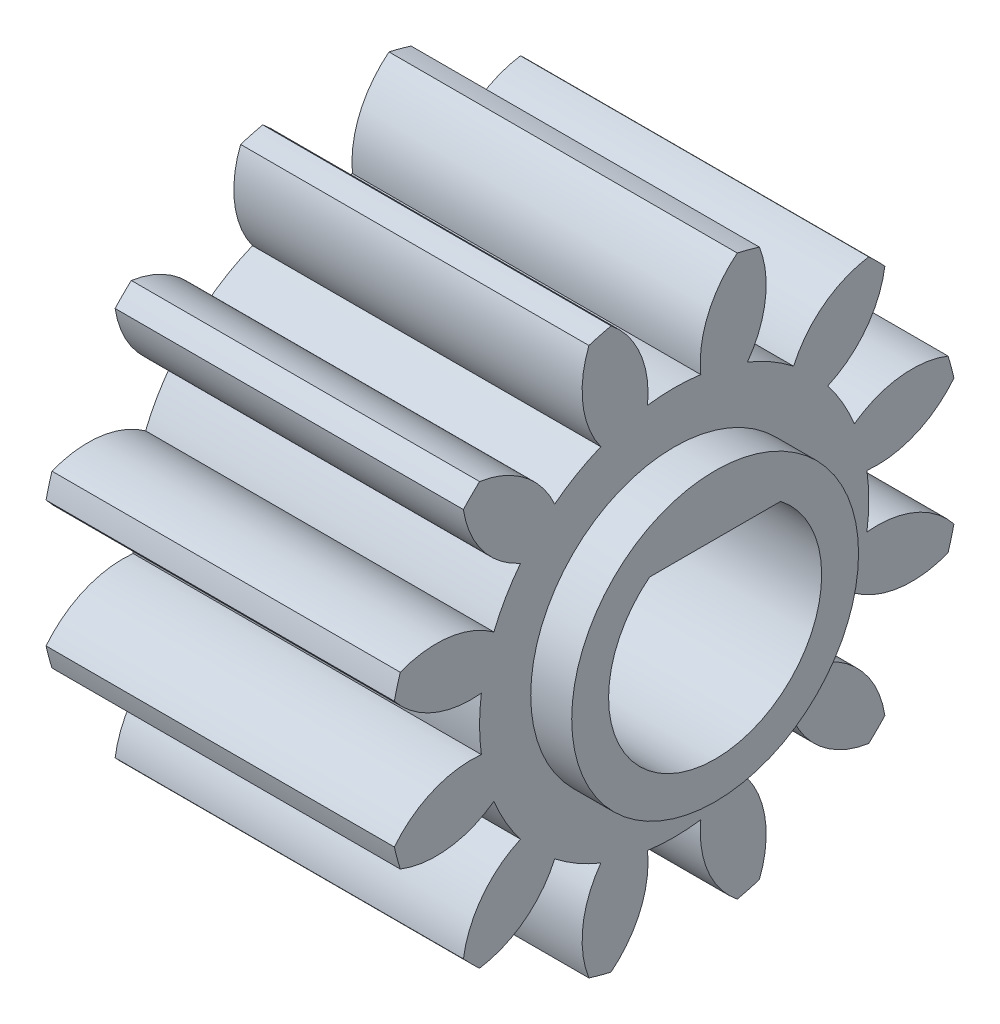
SolidWorks part; units mm, degrees
ref_plane "Plane1" through (0, 0, 0) normal (0, 0, 1) x (1, 0, 0)
ref_plane "Plane2" through (0, 0, 0) normal (0, 1, 0) x (1, 0, 0)
ref_plane "Plane3" through (0, 0, 0) normal (1, 0, 0) x (0, 0, -1)
sketch "HoldingSke" plane through (0, 0, 0) normal (0, 1, 0) x (1, 0, 0)
  line L0 (0, 0) -> (0.9781, -0.2079)
  line L1 (-15, 0) -> (100, 0) construction
  line L2 (0, 0) -> (-2.1039, 2.3779)
  line L3 (0, 0) -> (-11.863, 4.5341)
  line L4 (0, 0) -> (8.4473, 1.7955)
  line L5 (0, 0) -> (-46.8476, -17.4728)
  line L6 (0, 0) -> (-8.2896, -5.593)
  line L7 (-2.1039, 2.3779) -> (8.6586, 51.2059)
  line L8 (-76.2, 54.61) -> (-75.3, 54.61)
  line L9 (-67.7845, 28.3722) -> (-49.3413, 33.142)
  line L10 (-76.2, 71.12) -> (104.1128, 71.12)
  line L11 (0, 0) -> (-10, 0)
  line L12 (-76.2, 101.6) -> (-76.162, 101.6)
  line L13 (24.9733, 27.94) -> (52.9518, 28.4284)
  line L14 (24.9733, 27.94) -> (24.9743, 27.94)
  line L15 (24.9733, 27.94) -> (100.4006, 29.5858)
  line L16 (-63.627, -1) -> (-12.827, -1)
  circle A0 centre (0, 0) radius 2.5
  circle A1 centre (0, 0) radius 4.749
  circle A2 centre (0, 0) radius 37.5
  circle A3 centre (0, 0) radius 2.5
  dimension "Num_teeth" = 12
  dimension "Pitch_radius" = 180.3128
  dimension "Width" = 10
sketch "BasProSke" plane through (0, 0, 0) normal (0, 1, 0) x (1, 0, 0)
  line L0 (-10, 0) -> (60, 0) construction
  line L1 (0, 0) -> (0, 7)
  line L2 (0, 0) -> (8.5, 0)
  line L3 (8.5, 0) -> (8.5, 7)
  line L4 (8.5, 7) -> (0, 7)
  dimension "Thickness" = 8.5
  dimension "Diameter" = 14
revolve "Base-Revolve" add sketch "BasProSke" angle 360 about L0
sketch "TooCutSke" plane through (0, 0, 0) normal (1, 0, 0) x (0, 0, -1)
  line L1 (0, 0) -> (0, 107) construction
  line L2 (0, 0) -> (-0.8496, 5.9395) construction
  line L3 (0, 0) -> (-3.0836, 11.5081) construction
  line L4 (-0.8496, 5.9395) -> (-1.5418, 5.7541) construction
  arc A0 (0.6497, 4.7044) -> (-0.6497, 4.7044) centre (0, 0) ccw
  arc A1 (1.5664, 6.8486) -> (-1.5664, 6.8486) centre (0, 0) ccw
  circle A2 centre (0, 0) radius 6 construction
  circle A3 centre (0, 0) radius 5.8089 construction
  arc A4 (-0.6497, 4.7044) -> (-1.5664, 6.8486) centre (-3.0369, 4.9518) ccw
  arc A5 (1.5664, 6.8486) -> (0.6497, 4.7044) centre (3.0369, 4.9518) ccw
extrude "ToothCut" cut sketch "TooCutSke" along normal through all
fillet "Breaks" [suppressed] radius 0.02 tangent propagation no
fillet "RootFillets" [suppressed] radius 0.251
pattern_circular "TeethCuts" count 12 every 30 about axis through (-10, 0, 0) along (1, 0, 0) of "ToothCut", "RootFillets", "Breaks"
sketch "HubNeaOneSke" plane through (0, 0, 0) normal (-1, 0, 0) x (0, 0, 1)
  circle A0 centre (0, 0) radius 4.749
  dimension "Diameter" = 9.498
extrude "HubNearOne" [suppressed] add sketch "HubNeaOneSke" along normal blind 41.5001
sketch "HubNeaBotSke" plane through (0, 0, 0) normal (-1, 0, 0) x (0, 0, 1)
  circle A0 centre (0, 0) radius 4.749
  dimension "Diameter" = 9.498
extrude "HubNearBoth" [suppressed] add sketch "HubNeaBotSke" along normal blind 20.75
ref_plane "FarPln" through (8.5, 0, 0) normal (1, 0, 0) x (0, 0, -1)
sketch "HubFarSke" plane through (8.5, 0, 0) normal (1, 0, 0) x (0, 0, -1)
  circle A0 centre (0, 0) radius 4.749
  dimension "Diameter" = 9.498
extrude "HubFar" [suppressed] add sketch "HubFarSke" along normal blind 20.75
sketch "BorSke" plane through (0, 0, 0) normal (1, 0, 0) x (0, 0, -1)
  circle A0 centre (0, 0) radius 2.6
  dimension "Diameter" = 5.2
extrude "Bore" cut sketch "BorSke" along normal mid plane 100.0001
sketch "KeySke" plane through (0, 0, 0) normal (1, 0, 0) x (0, 0, -1)
  line L0 (-1, 0) -> (-1, 3.4)
  line L1 (-1, 3.4) -> (1, 3.4)
  line L2 (1, 3.4) -> (1, 0)
  line L3 (0, 0) -> (0, 34) construction
  line L4 (-1, 0) -> (1, 0)
  dimension "Width" = 2
extrude "Keyway" [suppressed] cut sketch "KeySke" along normal mid plane 100.0001
pattern_circular "Keyway2" [suppressed] count 2 every 90 about axis through (-10, 0, 0) along (1, 0, 0) reverse direction yes
sketch "Sketch1" plane through (8.5, 0, 0) normal (1, 0, 0) x (0, 0, -1)
  line L0 (-1.5992, 2.05) -> (1.5992, 2.05)
  circle A0 centre (0, 0) radius 2.6 construction
  arc A1 (1.5992, 2.05) -> (-1.5992, 2.05) centre (0, 0) ccw
  dimension "D1" = 2.05
extrude "Boss-Extrude1" add sketch "Sketch1" against normal up to surface (8.5 mm away) up to face at (0, 0, -2.6)
sketch "Sketch2" plane through (8.5, 0, 0) normal (1, 0, 0) x (0, 0, -1)
  line L0 (-1.5992, 2.05) -> (1.5992, 2.05) construction
  line L1 (-1.5992, 2.05) -> (1.5992, 2.05)
  circle A0 centre (0, 0) radius 3.5
  arc A1 (-1.5992, 2.05) -> (1.5992, 2.05) centre (0, 0) ccw construction
  arc A2 (-1.5992, 2.05) -> (1.5992, 2.05) centre (0, 0) ccw
  dimension "D1" = 7
extrude "Boss-Extrude2" add sketch "Sketch2" along normal blind 1
equation "' \"Module@HoldingSke\" = 6.35"
equation "' \"Num_teeth@HoldingSke\" = 12"
equation "' \"Ap@HoldingSke\" =  20"
equation "' \"Ap@HoldingSke\" = 20"
equation "' \"Width@HoldingSke\" = 0.5 * 25.4"
equation "' \"Hub_dia@HoldingSke\"= 1 * 25.4"
equation "' \"Hub_dia@HoldingSke\" = 1 * 25.4"
equation "' \"Overall_len@HoldingSke\" = 1.0 * 25.4"
equation "' \"Bore@HoldingSke\" = 0.75 * 25.4"
equation "' \"T_dim@HoldingSke\" = 0.1 * 25.4"
equation "' \"Width@KeySke\" = 0.25 * 25.4"
equation "' \"Show_teeth@HoldingSke\" = 13"
equation "' \"Backlash@HoldingSke\" = 0.009 * 25.4"
equation "' \"Addendum_fac@HoldingSke\" = 1.0"
equation "' \"Dedendum_fac@HoldingSke\" = 1.25"
equation "' \"Dedendum_add@HoldingSke\" = 0.00005 * 25.4"
equation "' \"Clearance_fac@HoldingSke\" = 0.25"
equation "\"Pitch@HoldingSke\" = 1 / \"Module@HoldingSke\""
equation "\"Overcut_dia@TooCutSke\" = (\"Num_teeth@HoldingSke\" + 2 * \"Addendum_fac@HoldingSke\") / \"Pitch@HoldingSke\" + 0.002 * 25.4"
equation "\"Pitch_dia@TooCutSke\" = \"Num_teeth@HoldingSke\" / \"Pitch@HoldingSke\""
equation "\"Base_dia@TooCutSke\" = \"Num_teeth@HoldingSke\" / \"Pitch@HoldingSke\" * cos((\"Ap@HoldingSke\"  * 3.14159265 / 180))"
equation "\"Root_dia@TooCutSke\" = (\"Num_teeth@HoldingSke\" + 2) / \"Pitch@HoldingSke\" - 2 * (\"Addendum_fac@HoldingSke\" + \"Dedendum_fac@HoldingSke\") / \"Pitch@HoldingSke\" - \"Dedendum_add@HoldingSke\" * 2"
equation "\"Half_ang@TooCutSke\" = 180 / \"Num_teeth@HoldingSke\""
equation "\"Half_CT@TooCutSke\" = \"Num_teeth@HoldingSke\" / \"Pitch@HoldingSke\" * sin((3.14159265 / 2 / \"Num_teeth@HoldingSke\")) / 2 - 7 * \"Backlash@HoldingSke\" / 4"
equation "\"Flank_rad@TooCutSke\" = \"Num_teeth@HoldingSke\" / \"Pitch@HoldingSke\" / 5"
equation "\"Radius@RootFillets\" = \"Clearance_fac@HoldingSke\" / \"Pitch@HoldingSke\" + \"Dedendum_add@HoldingSke\""
equation "\"Break_rad@Breaks\" = 0.02 / \"Pitch@HoldingSke\""
equation "\"Thickness@HoldingSke\" = \"Width@HoldingSke\""
equation "\"OAL@HoldingSke\" = \"Thickness@HoldingSke\""
equation "\"MHD@HoldingSke\" = (\"Num_teeth@HoldingSke\" + 2) / \"Pitch@HoldingSke\" - 2 * (\"Addendum_fac@HoldingSke\" + \"Dedendum_fac@HoldingSke\")  / \"Pitch@HoldingSke\" - \"Dedendum_add@HoldingSke\" * 2"
equation "\"MBD@HoldingSke\" = (\"Num_teeth@HoldingSke\" + 2) / \"Pitch@HoldingSke\" - 2 * (\"Addendum_fac@HoldingSke\" + \"Dedendum_fac@HoldingSke\")  / \"Pitch@HoldingSke\" - \"Dedendum_add@HoldingSke\" * 2 - 0.002 * 25.4"
equation "\"MHD@HoldingSke\" = ((sgn( \"MHD@HoldingSke\" - \"Hub_dia@HoldingSke\" )-1)*( \"MHD@HoldingSke\" - \"Hub_dia@HoldingSke\" ))/-2+ \"Hub_dia@HoldingSke\""
equation "\"MBD@HoldingSke\" = ((sgn( \"MBD@HoldingSke\" - \"Bore@HoldingSke\" )-1)*( \"MBD@HoldingSke\" - \"Bore@HoldingSke\" ))/-2+ \"Bore@HoldingSke\""
equation "\"OAL@HoldingSke\" = ((sgn( \"OAL@HoldingSke\" - \"Overall_len@HoldingSke\" )+1)*( \"OAL@HoldingSke\" - \"Overall_len@HoldingSke\" ))/2 + \"Overall_len@HoldingSke\" + 0.000002 * 25.4"
equation "\"Num_teeth@TeethCuts\" = int( \"Show_teeth@HoldingSke\" ) + 1"
equation "\"Num_teeth@TeethCuts\" = ((sgn( \"Num_teeth@TeethCuts\" - \"Num_teeth@HoldingSke\" )-1)*( \"Num_teeth@TeethCuts\" - \"Num_teeth@HoldingSke\" ))/-2+ \"Num_teeth@HoldingSke\""
equation "\"Num_teeth@TeethCuts\" = ((sgn( \"Num_teeth@TeethCuts\" - 2.0)+1)*( \"Num_teeth@TeethCuts\" - 2.0))/2 +2.0"
equation "\"Angle@TeethCuts\" = 360.0 / \"Num_teeth@HoldingSke\""
equation "\"Diameter@BasProSke\" = (\"Num_teeth@HoldingSke\" + 2 * \"Addendum_fac@HoldingSke\") / \"Pitch@HoldingSke\""
equation "' \"Fillet_rad@BasProSke\" =  \"Thickness@HoldingSke\" * 0.05"
equation "' \"Fillet_rad@BasProSke\" = \"Thickness@HoldingSke\" * 0.05"
equation "\"MHD@HoldingSke\" = ((sgn( \"MHD@HoldingSke\" - \"Root_dia@TooCutSke\" )-1)*( \"MHD@HoldingSke\" - \"Root_dia@TooCutSke\" ))/-2+ \"Root_dia@TooCutSke\""
equation "\"Diameter@HubNeaOneSke\" = \"MHD@HoldingSke\""
equation "\"Length@HubNearOne\" = \"OAL@HoldingSke\" - \"Thickness@BasProSke\""
equation "\"Diameter@HubNeaBotSke\" = \"MHD@HoldingSke\""
equation "\"Length@HubNearBoth\" = ( \"OAL@HoldingSke\" - \"Thickness@BasProSke\" ) / 2.0"
equation "\"Thickness@FarPln\" = \"Thickness@BasProSke\""
equation "\"Diameter@HubFarSke\" = \"MHD@HoldingSke\""
equation "\"Length@HubFar\" = ( \"OAL@HoldingSke\" - \"Thickness@BasProSke\" ) / 2.0"
equation "\"D1@Bore\" = \"OAL@HoldingSke\" * 2.0"
equation "\"D1@Keyway\" = \"OAL@HoldingSke\" * 2.0"
equation "\"Offset@KeySke\" = \"T_dim@HoldingSke\" + \"MBD@HoldingSke\" / 2.0"
